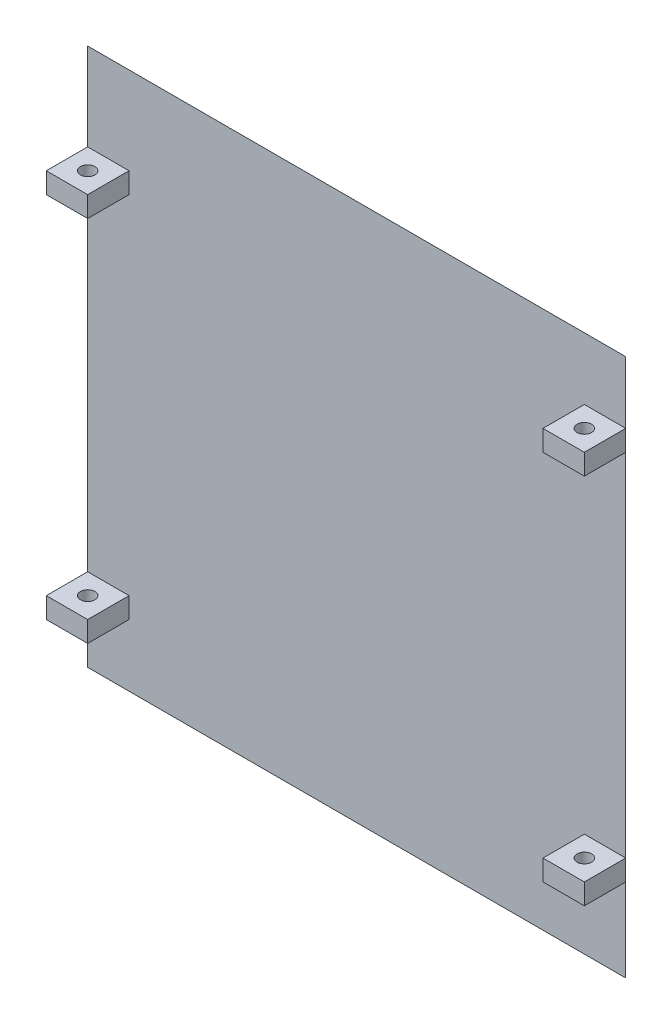
SolidWorks part; units mm, degrees
ref_plane "Plan de face" through (0, 0, 0) normal (0, 0, 1) x (1, 0, 0)
ref_plane "Plan de dessus" through (0, 0, 0) normal (0, 1, 0) x (1, 0, 0)
ref_plane "Plan de droite" through (0, 0, 0) normal (1, 0, 0) x (0, 0, -1)
sketch "Esquisse1" plane through (0, 0, 0) normal (0, 0, 1) x (1, 0, 0)
  line L1 (0, 130) -> (130, 130)
  line L2 (0, 130) -> (0, 0)
  line L3 (0, 0) -> (130, 0)
  line L4 (130, 130) -> (130, 0)
  dimension "D1" = 130
  dimension "D2" = 130
extrude "Boss.-Extru.1" add sketch "Esquisse1" along normal blind 3
chamfer "Chanfrein1" distance 3 angle 45 4 edges at (65, 130, 0) (130, 65, 0) (65, 0, 0) (0, 65, 0)
sketch "Esquisse2" plane through (0, 0, 3) normal (0, 0, 1) x (1, 0, 0)
  line L0 (0, 108.9) -> (10, 108.9)
  line L1 (0, 20) -> (10, 20)
  line L2 (0, 20) -> (0, 15)
  line L3 (0, 15) -> (10, 15)
  line L4 (10, 20) -> (10, 15)
  line L5 (0, 108.9) -> (0, 103.9)
  line L6 (130, 20.1) -> (120, 20.1)
  line L7 (130, 20.1) -> (130, 25.1)
  line L8 (130, 25.1) -> (120, 25.1)
  line L9 (120, 20.1) -> (120, 25.1)
  line L10 (0, 103.9) -> (10, 103.9)
  line L11 (0, 0) -> (130, 0) construction
  line L12 (10, 108.9) -> (10, 103.9)
  line L13 (130, 110) -> (120, 110)
  line L14 (130, 110) -> (130, 115)
  line L15 (130, 115) -> (120, 115)
  line L16 (120, 110) -> (120, 115)
  line L17 (130, 130) -> (0, 130) construction
  line L18 (130, 0) -> (130, 130) construction
  line L19 (0, 130) -> (0, 0) construction
  dimension "D1" = 10
  dimension "D2" = 5
  dimension "D3" = 5
  dimension "D4" = 10
  dimension "D5" = 20.1
  dimension "D6" = 15
  dimension "D7" = 10
  dimension "D8" = 5
  dimension "D9" = 5
  dimension "D10" = 10
  dimension "D11" = 21.1
  dimension "D12" = 15
extrude "Boss.-Extru.2" add sketch "Esquisse2" along normal blind 10
sketch "Esquisse4" plane through (0, 15, 0) normal (0, -1, 0) x (1, 0, 0)
  circle A0 centre (5, 8) radius 1.75
  dimension "D1" = 3.5
extrude "Enlèv. mat.-Extru.1" cut sketch "Esquisse4" against normal through all
sketch "Esquisse5" plane through (0, 20.1, 0) normal (0, -1, 0) x (1, 0, 0)
  circle A0 centre (125, 8) radius 1.75
  dimension "D1" = 3.5
extrude "Enlèv. mat.-Extru.2" cut sketch "Esquisse5" against normal through all
sketch "Esquisse6" plane through (0, 0, 0) normal (0, 0, -1) x (-1, 0, 0)
  spline S0 degree 3 poles (-52.2608, 57.8421) (-49.6384, 61.8272) (-44.8313, 69.6151) (-48.8728, 80.145) (-54.9071, 83.5437) (-60.9931, 84.98) (-64.0267, 86.078) (-73.2308, 84.9688) (-69.0425, 86.0299) (-67.3422, 86.2496) (-60.1575, 85.7216) (-64.3186, 86.4762) (-66.4423, 86.3336) (-70.1075, 86.4431) (-74.9061, 86.0103) (-83.3803, 84.5765) (-94.1618, 79.7016) (-96.7562, 78.5435) (-98.2506, 78.108) (-98.9585, 77.6571) (-99.8526, 77.5525) (-101.8465, 77.6089) (-103.5008, 75.5297) (-107.1721, 74.4748) (-108.9628, 73.6611) (-110.3602, 72.7038) (-110.3319, 73.7668) (-109.3967, 73.7194) (-107.9155, 74.7442) (-106.8431, 74.9971) (-105.283, 75.8669) (-105.6891, 75.987) (-106.0803, 75.6117) (-105.9136, 75.9032) (-105.8421, 76.0206) (-105.8389, 76.0258) knots 0 0 0 0 0.034118 0.050236 0.068967 0.0735 0.095563 0.104191 0.107922 0.116908 0.126964 0.13031 0.137621 0.14482 0.154993 0.171422 0.207781 0.216896 0.21919 0.229442 0.232265 0.24613 0.386673 0.489154 0.601852 0.608768 0.628384 0.656974 0.686943 0.800375 0.806976 0.814482 0.827885 0.837106 0.837535 0.837535 0.837535 0.837535
  spline S1 degree 3 poles (-105.8389, 76.0258) (-100.6118, 77.9155) (-100.2702, 80.5161) (-93.2482, 82.1418) (-93.5638, 82.5743) (-93.9678, 82.3368) (-94.8208, 81.8094) (-97.6014, 80.8964) (-101.5982, 79.2221) (-106.3195, 76.8668) (-108.7701, 75.8401) (-110.3344, 74.7942) (-110.3141, 75.4361) (-109.8085, 75.438) (-109.3206, 75.9394) (-108.2749, 76.212) (-107.1591, 77.0531) (-105.9218, 77.5549) (-105.3139, 77.9637) (-104.8184, 78.2019) (-105.231, 78.5203) (-105.4612, 78.1801) (-105.7387, 77.9687) (-106.081, 78.2142) (-105.6102, 78.2858) (-105.3297, 78.5884) (-104.4932, 78.8863) (-103.493, 79.6647) (-102.3098, 80.2988) (-101.5517, 80.5797) (-101.2449, 80.9764) (-102.0347, 80.857) (-102.3818, 80.3241) (-103.3876, 80.0346) (-103.7792, 79.5393) (-104.2616, 79.5228) (-104.1311, 79.9341) (-103.6309, 80.0142) (-103.0502, 80.5173) (-101.4726, 81.8937) (-96.4487, 84.7742) (-84.9307, 90.5917) (-71.9561, 93.446) (-62.8864, 94.0636) (-61.0834, 94.142) (-60.887, 94.1791) (-60.6433, 94.3623) (-61.1154, 94.5269) (-61.6373, 94.309) (-62.3993, 94.3521) (-62.6856, 94.3191) knots 0 0 0 0 0.134848 0.143034 0.144602 0.148639 0.15418 0.178068 0.234678 0.292201 0.330746 0.333193 0.337239 0.34163 0.346585 0.358072 0.373748 0.389768 0.396913 0.399366 0.402749 0.405986 0.410304 0.412056 0.415103 0.419095 0.426513 0.440579 0.458948 0.465949 0.467501 0.470952 0.480464 0.491217 0.499184 0.500837 0.502285 0.509316 0.515196 0.525664 0.573905 0.691977 0.923329 0.972552 0.974531 0.977935 0.97947 0.981332 0.988582 1 1 1 1
  spline S2 degree 3 poles (-62.6856, 94.3191) (-62.6995, 94.3318) (-64.7884, 94.2314) (-65.8524, 94.0279) (-66.0369, 94.1225) (-65.9086, 94.4036) (-65.798, 94.3896) (-65.6216, 94.3896) knots 0 0 0 0 0.789101 0.825842 0.866785 0.917494 1 1 1 1
  spline S3 degree 3 poles (-65.6216, 94.3896) (-63.2585, 94.6704) (-59.495, 95.1875) (-52.0827, 94.2442) (-43.7057, 92.2507) (-37.2179, 83.72) (-37.2855, 77.1602) (-37.3013, 71.7693) (-39.1364, 68.9841) (-39.8729, 66.5169) (-39.3287, 65.3075) (-41.0595, 63.9121) (-42.4559, 61.7981) (-43.6333, 60.226) (-45.9488, 58.4638) (-41.8796, 58.9786) (-38.748, 58.2737) (-32.4318, 56.8411) (-24.5604, 47.5635) (-31.2716, 29.0772) (-45.0689, 18.0303) (-54.4708, 12.0253) (-59.2034, 10.2188) (-60.4918, 10.394) (-61.9515, 10.3691) (-65.7015, 10.1002) (-62.7216, 10.9264) (-60.4262, 12.5605) (-54.8067, 15.1884) (-46.9357, 20.5539) (-38.0852, 28.4186) (-33.5313, 36.6172) (-31.8782, 43.5728) (-35.516, 45.7137) (-37.6403, 46.9214) (-40.9409, 46.4042) (-40.7784, 47.5282) (-40.889, 48.4724) (-43.3977, 47.6637) (-46.2427, 49.1704) (-50.6768, 48.1795) (-53.5787, 48.5526) (-55.4108, 47.7347) (-55.9303, 48.6307) (-54.7275, 48.5368) (-53.3968, 48.5489) (-54.309, 49.4357) (-55.2096, 48.6885) (-57.1123, 49.1108) (-58.4073, 46.5423) (-61.4517, 46.1535) (-63.7617, 43.1218) (-68.0611, 42.1645) (-72.4721, 39.1024) (-74.9346, 38.4105) (-78.6308, 35.6245) (-78.3288, 37.0446) (-77.2601, 37.0218) (-76.3943, 37.9424) (-75.255, 38.5522) (-73.9425, 38.9825) (-73.1359, 40.268) (-71.3255, 40.7682) (-69.4422, 41.8375) (-68.4876, 42.74) (-66.7853, 43.8361) (-68.3636, 43.2945) (-68.8586, 42.5676) (-70.2974, 41.8015) (-71.5952, 40.8384) (-73.4687, 40.2589) (-75.8765, 38.8388) (-76.9669, 37.3127) (-79.3015, 36.9431) (-78.9857, 37.3002) (-78.9792, 37.2159) (-78.6822, 37.3526) knots 0 0 0 0 0.026687 0.041759 0.083493 0.118973 0.15054 0.156598 0.176995 0.180173 0.185825 0.19148 0.201603 0.213818 0.218107 0.223796 0.242243 0.2661 0.288782 0.36971 0.440445 0.490023 0.491708 0.496504 0.503315 0.512758 0.517467 0.527117 0.549028 0.582505 0.635087 0.675369 0.692164 0.702026 0.71711 0.724427 0.726292 0.728748 0.733278 0.748051 0.765921 0.779575 0.782783 0.784337 0.788152 0.791967 0.793474 0.798863 0.80206 0.813838 0.823241 0.834393 0.853281 0.871386 0.888313 0.896676 0.897774 0.902185 0.905809 0.911659 0.916426 0.920643 0.927543 0.936656 0.942844 0.946607 0.949758 0.954208 0.957935 0.967061 0.972246 0.979627 0.996876 0.997506 0.998263 1 1 1 1
  spline S4 degree 3 poles (-78.6822, 37.3526) (-78.6465, 37.5198) (-78.8901, 37.39) (-79.2406, 37.4223) (-78.875, 37.7358) (-78.4496, 38.0129) (-77.4061, 38.5858) (-76.0491, 39.8696) (-73.3427, 42.2223) (-69.7805, 44.6682) (-65.7556, 45.6902) (-65.014, 47.0156) (-64.9107, 47.1869) (-65.3567, 47.2925) (-65.6831, 46.9722) (-66.449, 46.8791) (-67.2953, 46.8275) (-68.3511, 47.2196) (-69.5257, 47.3086) (-72.1647, 46.9293) (-75.5127, 45.8708) (-79.6775, 44.1113) (-82.623, 42.9702) (-84.5469, 42.117) (-85.0648, 41.2666) (-86.014, 41.5045) (-86.8195, 40.9778) (-87.9561, 40.7765) (-88.8809, 40.267) (-90.0148, 40.1344) (-90.8347, 39.5832) (-91.7251, 39.3848) (-92.6493, 39.4342) (-92.9137, 40.4373) (-92.0235, 41.4239) (-90.6549, 42.9516) (-87.5388, 44.4468) (-83.8693, 45.9769) (-80.5041, 48.9266) (-77.0018, 49.9201) (-74.0848, 51.5014) (-72.2033, 51.5734) (-70.7106, 52.9269) (-70.3706, 52.1705) (-70.9533, 51.5804) (-69.6511, 52.0206) (-69.0083, 52.4602) (-67.8221, 53.3021) (-66.4801, 53.6928) (-65.0968, 53.9449) (-64.6302, 55.1427) (-63.5259, 54.8911) (-62.3783, 55.4176) (-60.9333, 56.519) (-58.4124, 56.6795) (-55.4998, 57.3609) (-53.3644, 57.4178) (-52.2608, 57.8421) knots 0 0 0 0 0.003835 0.005626 0.00865 0.013337 0.025485 0.043794 0.074034 0.138519 0.186487 0.188036 0.18927 0.191769 0.197818 0.204074 0.215307 0.224789 0.239449 0.252379 0.309643 0.350812 0.396295 0.411559 0.416285 0.42557 0.437284 0.446181 0.46202 0.470349 0.48205 0.492444 0.500051 0.507958 0.519114 0.539936 0.574207 0.626742 0.667092 0.713693 0.742758 0.767935 0.781266 0.784831 0.790075 0.797681 0.809789 0.823175 0.84057 0.856115 0.863527 0.876386 0.884884 0.903947 0.932867 0.962689 1 1 1 1
  point P34 (-63.4359, 51.9284)
  point P97 (-38.9435, 79.973)
extrude "Enlèv. mat.-Extru.3" cut sketch "Esquisse6" against normal blind 2.6
sketch3d "Esquisse3D2" plane through (0, 0, 0) normal (0, 0, 1) x (1, 0, 0)
